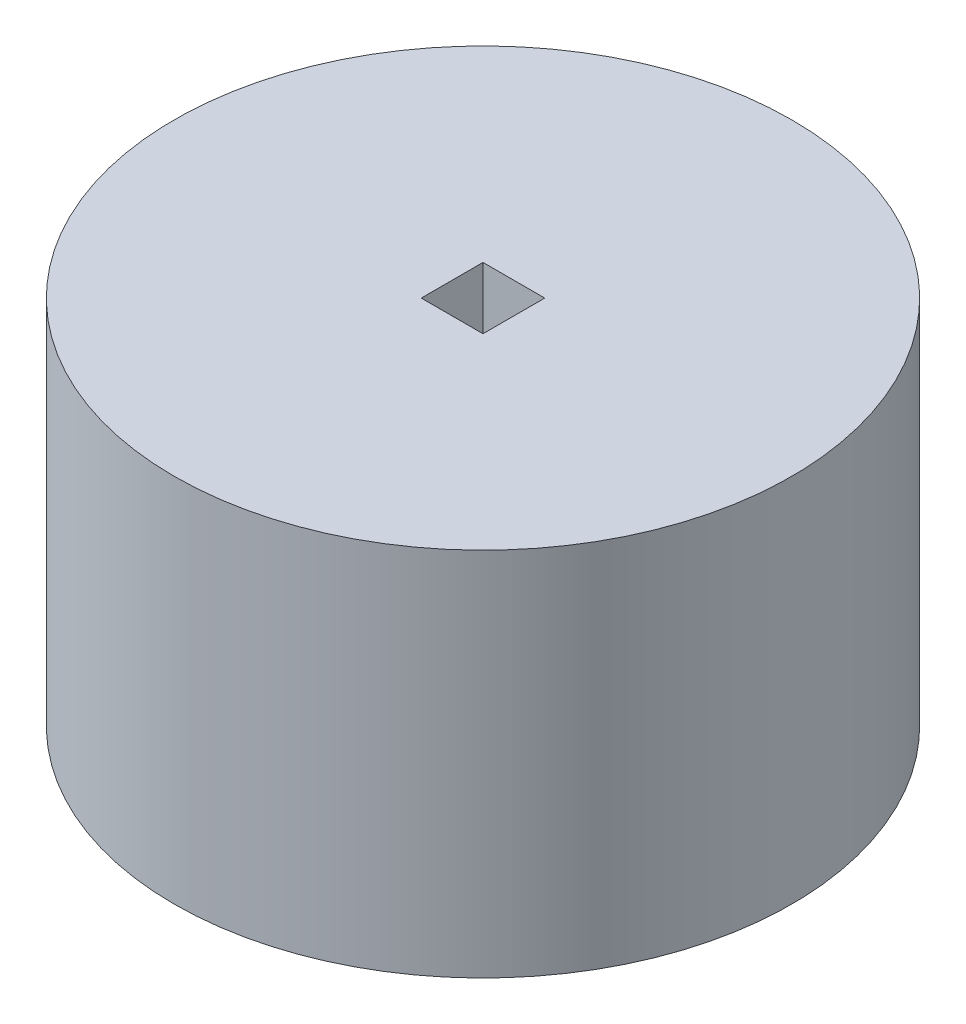
SolidWorks part; units mm, degrees
ref_plane "Front Plane" through (0, 0, 0) normal (0, 0, 1) x (1, 0, 0)
ref_plane "Top Plane" through (0, 0, 0) normal (0, 1, 0) x (1, 0, 0)
ref_plane "Right Plane" through (0, 0, 0) normal (1, 0, 0) x (0, 0, -1)
sketch "Sketch1" plane through (0, 0, 0) normal (0, 1, 0) x (1, 0, 0)
  circle A0 centre (0, 0) radius 25
  dimension "D1" = 50
extrude "Boss-Extrude1" add sketch "Sketch1" along normal blind 30
sketch "Sketch2" plane through (0, 0, 0) normal (0, -1, 0) x (1, 0, 0)
  circle A0 centre (0, 0) radius 13.1
  dimension "D1" = 26.2
extrude "Cut-Extrude1" cut sketch "Sketch2" against normal blind 7.9
sketch "Sketch3" plane through (0, 30, 0) normal (0, 1, 0) x (1, 0, 0)
  circle A0 centre (0, 0) radius 1.5
  dimension "D1" = 3
extrude "Cut-Extrude2" cut sketch "Sketch3" against normal through all
sketch "Sketch4" plane through (0, 30, 0) normal (0, 1, 0) x (1, 0, 0)
  line L1 (-2.5, -2.5) -> (2.5, -2.5)
  line L2 (-2.5, -2.5) -> (-2.5, 2.5)
  line L3 (-2.5, 2.5) -> (2.5, 2.5)
  line L4 (2.5, -2.5) -> (2.5, 2.5)
  line L5 (-2.5, -2.5) -> (2.5, 2.5) construction
  line L6 (-2.5, 2.5) -> (2.5, -2.5) construction
  point P0 (0, 0)
  dimension "D1" = 5
  dimension "D2" = 5
extrude "Cut-Extrude3" cut sketch "Sketch4" against normal blind 10
